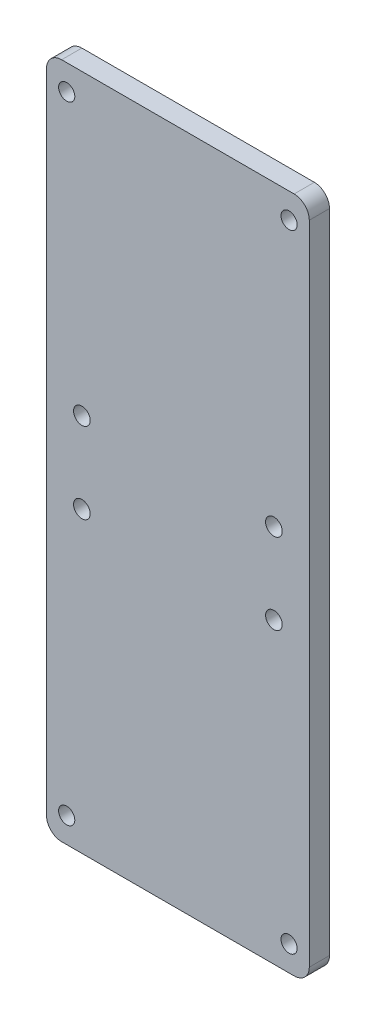
SolidWorks part; units mm, degrees
material "Acrylic (Medium-high impact)"
ref_plane "Front Plane" through (0, 0, 0) normal (0, 0, 1) x (1, 0, 0)
ref_plane "Top Plane" through (0, 0, 0) normal (0, 1, 0) x (1, 0, 0)
ref_plane "Right Plane" through (0, 0, 0) normal (1, 0, 0) x (0, 0, -1)
sketch "Sketch1" plane through (0, 0, 0) normal (0, 0, 1) x (1, 0, 0)
  line L0 (1.25, 62.9364) -> (93.1655, 62.9364) construction
  line L1 (23.2069, 126.9364) -> (23.2069, -1.0636)
  line L2 (26.2069, 129.9364) -> (72.2085, 129.9364)
  line L3 (71.2085, 0.9364) -> (71.2085, -12.0636) construction
  line L4 (26.2069, -4.0636) -> (72.2085, -4.0636)
  line L8 (49.2077, -12.0636) -> (49.2077, 137.9364) construction
  line L20 (75.2085, 126.9364) -> (75.2085, -1.0636)
  circle A0 centre (30.2077, 54.9364) radius 1.65
  circle A1 centre (27.2069, 0.9364) radius 1.6
  arc A2 (26.2069, -4.0636) -> (23.2069, -1.0636) centre (26.2069, -1.0636) cw
  circle A3 centre (68.2077, 70.9364) radius 1.65
  arc A4 (72.2085, -4.0636) -> (75.2085, -1.0636) centre (72.2085, -1.0636) ccw
  circle A5 centre (71.2085, 124.9364) radius 1.6
  arc A6 (72.2085, 129.9364) -> (75.2085, 126.9364) centre (72.2085, 126.9364) cw
  circle A7 centre (71.2085, 0.9364) radius 1.6
  arc A8 (26.2069, 129.9364) -> (23.2069, 126.9364) centre (26.2069, 126.9364) ccw
  circle A9 centre (68.2077, 54.9364) radius 1.65
  circle A10 centre (27.2069, 124.9364) radius 1.6
  circle A11 centre (30.2077, 70.9364) radius 1.65
  point P10 (23.2069, 62.9364)
  point P13 (49.2077, 129.9364)
  point P14 (49.2077, -4.0636)
  point P30 (75.2085, 62.9364)
  dimension "D5" = 22.0008
  dimension "D17" = 3
  dimension "D6" = 3.2
  dimension "D7" = 16
  dimension "D8" = 19
  dimension "D2" = 26.0008
  dimension "D3" = 67
  dimension "D4" = 62
extrude "Boss-Extrude1" add sketch "Sketch1" along normal blind 4
